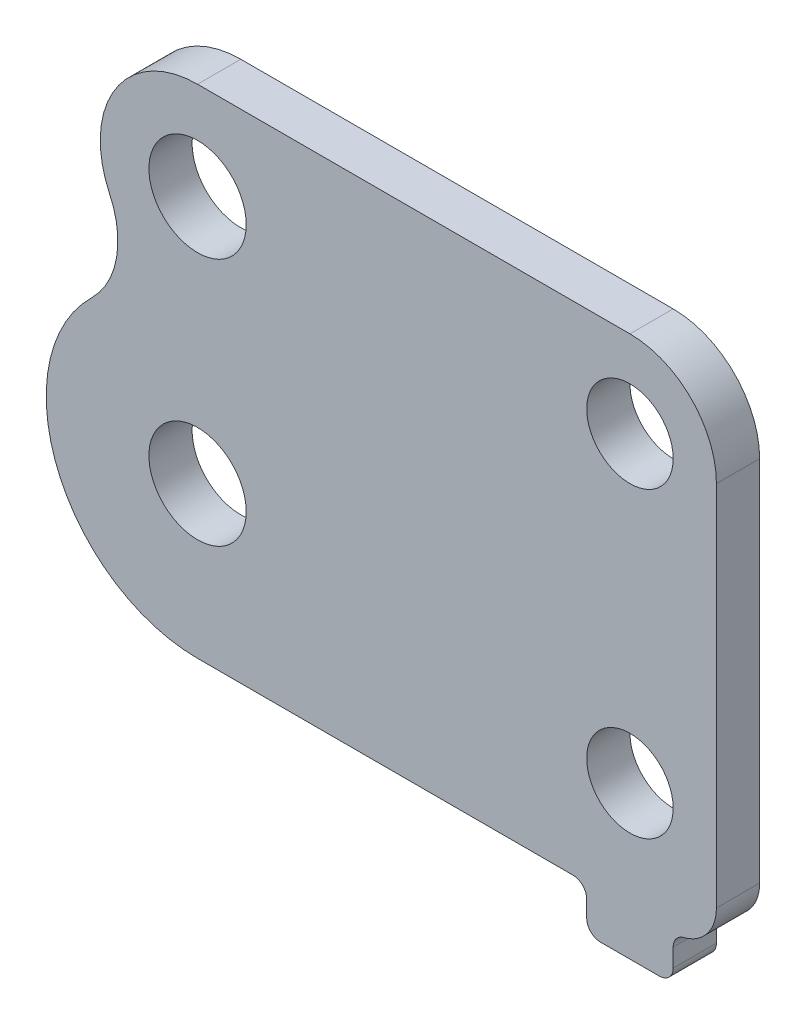
SolidWorks part; units mm, degrees
ref_plane "Front Plane" through (0, 0, 0) normal (0, 0, 1) x (1, 0, 0)
ref_plane "Top Plane" through (0, 0, 0) normal (0, 1, 0) x (1, 0, 0)
ref_plane "Right Plane" through (0, 0, 0) normal (1, 0, 0) x (0, 0, -1)
sketch "Sketch2" plane through (0, 0, 0) normal (0, 0, 1) x (1, 0, 0)
  line L0 (0, 5.5562) -> (12.7, 5.5562)
  line L1 (12.7, 5.5562) -> (12.7, -5.5562) construction
  line L2 (12.7, -5.5562) -> (0, -5.5562)
  line L3 (12.7, 5.5562) -> (12.7, 13.4938)
  line L4 (12.7, 13.4938) -> (19.05, 13.4937)
  line L5 (19.05, 13.4937) -> (19.05, -5.5562)
  line L6 (19.05, -5.5562) -> (12.7, -5.5562)
  line L7 (15.875, 9.525) -> (15.875, -1.5875) construction
  line L8 (14.2875, -5.5562) -> (14.2875, -7.1818)
  line L9 (14.2875, -7.1818) -> (17.4625, -7.1818)
  line L10 (17.4625, -7.1818) -> (17.4625, -5.5562)
  line L11 (0, 0) -> (0, -9.1281) construction
  line L12 (7.1437, 12.7) -> (12.7, 12.7)
  line L14 (12.7, 12.7) -> (19.05, 12.7)
  line L15 (0, 12.7) -> (7.1437, 12.7)
  circle A0 centre (0, 0) radius 1.7859
  circle A1 centre (0, 0) radius 5.5562
  circle A2 centre (0, 9.1281) radius 1.7859
  circle A3 centre (0, 9.1281) radius 3.5719
  circle A4 centre (0, 0) radius 9.1281 construction
  circle A5 centre (15.875, 9.525) radius 1.5875
  circle A6 centre (15.875, -1.5875) radius 1.5875
  circle A7 centre (-6.1005, 6.2465) radius 3.175
  circle A8 centre (7.1437, 9.1281) radius 3.5719
  circle A9 centre (0, 0) radius 12.7 construction
  circle A11 centre (7.1437, 9.1281) radius 1.7859 construction
  point P17 (15.875, 3.9688)
  point P18 (19.05, 3.9688)
  point P21 (15.875, -5.5562)
  point P25 (15.875, -7.1818)
  dimension "D1" = 3.5719
  dimension "D2" = 11.1125
  dimension "D5" = 7.1437
  dimension "D7" = 3.175
  dimension "D6" = 6.35
  dimension "D3" = 11.1125
  dimension "D4" = 6.35
  dimension "D8" = 3.175
  dimension "D9" = 1.6256
  dimension "D10" = 19.05
extrude "Boss-Extrude1" add sketch "Sketch2" along normal blind 1.5875 contours A1 L2 L6 L5 L4 L3 L0 A6 A5 | L9 L10 L6 L8 | A8 A3 L0 | A1 A0 | A8 A11 | A8 L0 L3 L12 | A7 A1 A3 | A3 A2 | A8 L15 A3 region at (3.5719, 6.3541, 0) region at (12.3012, 1.8224, 0) region at (3.8177, 3.8177, 0) region at (-1.8576, 6.1962, 0) region at (-2.3434, 5.6656, 0) region at (11.209, 9.1281, 0) region at (7.1438, 9.1281, 0) region at (3.5719, 11.9022, 0) region at (15.875, -6.369, 0)
fillet "Fillet1" radius 3.175 1 edges at (19.05, 12.7, 0.7937)
fillet "Fillet3" radius 1.5875 1 edges at (19.05, -5.5562, 0.7937)
fillet "Fillet2" radius 0.508 4 edges at (14.2875, -7.1818, 0.7937) (17.4625, -7.1818, 0.7937) (14.2875, -5.5562, 0.7937) (17.4625, -5.5562, 0.7937)
